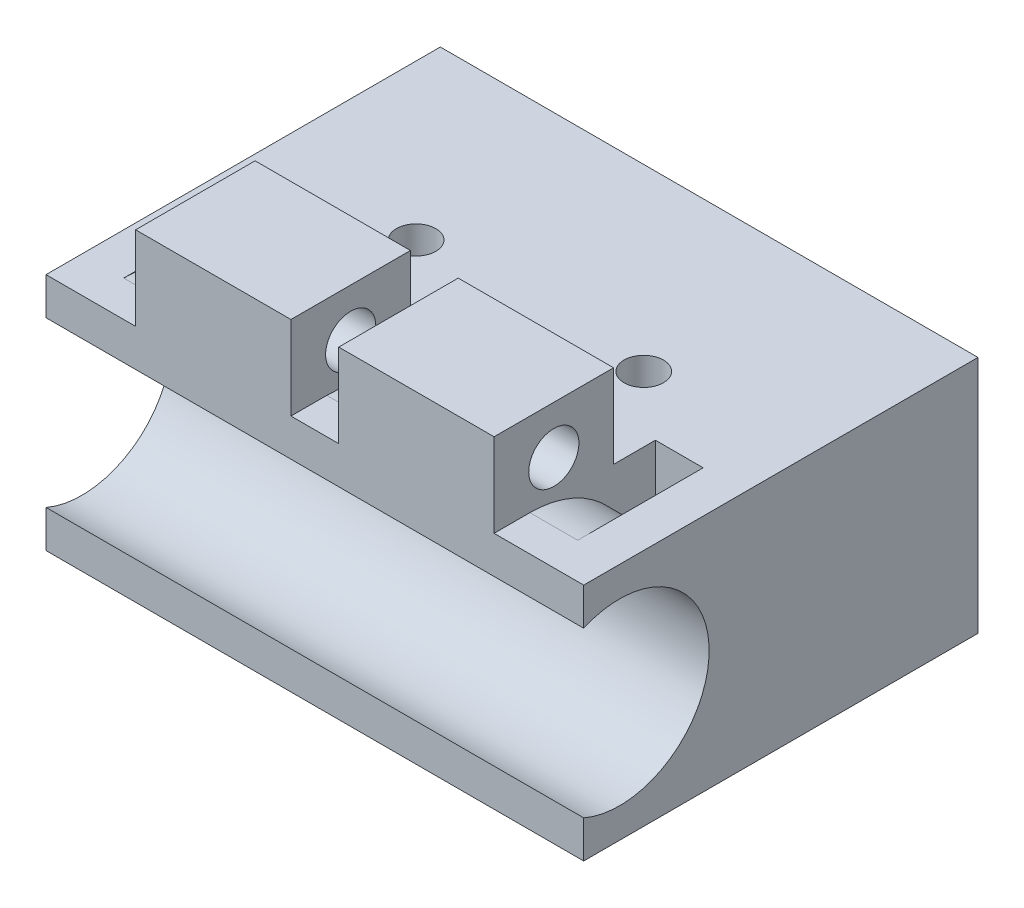
SolidWorks part; units mm, degrees
ref_plane "Front Plane" through (0, 0, 0) normal (0, 0, 1) x (1, 0, 0)
ref_plane "Top Plane" through (0, 0, 0) normal (0, 1, 0) x (1, 0, 0)
ref_plane "Right Plane" through (0, 0, 0) normal (1, 0, 0) x (0, 0, -1)
sketch "Sketch2" plane through (0, 0, 0) normal (0, 0, 1) x (1, 0, 0)
  line L1 (22.5, 10) -> (-22.5, 10)
  line L2 (22.5, 10) -> (22.5, -10)
  line L3 (22.5, -10) -> (-22.5, -10)
  line L4 (-22.5, 10) -> (-22.5, -10)
  line L5 (22.5, 10) -> (-22.5, -10) construction
  line L6 (22.5, -10) -> (-22.5, 10) construction
  point P0 (0, 0)
  dimension "D1" = 20
  dimension "D2" = 45
extrude "Boss-Extrude1" add sketch "Sketch2" along normal blind 33
sketch "Sketch3" plane through (22.5, 0, 0) normal (1, 0, 0) x (0, 0, -1)
  line L0 (-30, 0) -> (0, 0) construction
  circle A0 centre (-30, 0) radius 7.5
  dimension "D1" = 15
  dimension "D2" = 30
extrude "Cut-Extrude1" cut sketch "Sketch3" against normal blind 45
sketch "Sketch4" plane through (0, 0, 0) normal (0, 0, -1) x (-1, 0, 0)
  line L4 (22.5, -10) -> (22.5, 10)
  line L5 (22.5, 10) -> (-22.5, 10)
  line L6 (-22.5, 10) -> (-22.5, -10)
  line L7 (-22.5, -10) -> (22.5, -10)
  line L8 (22.5, -10) -> (22.5, 10)
  line L9 (22.5, 10) -> (-22.5, 10)
  line L10 (-22.5, 10) -> (-22.5, -10)
  line L11 (-22.5, -10) -> (22.5, -10)
  circle A0 centre (-15, 0) radius 4
  circle A1 centre (15, 0) radius 4
  dimension "D2" = 8
  dimension "D3" = 30
  dimension "D4" = 15
  dimension "D1" = 0
extrude "Cut-Extrude2" cut sketch "Sketch4" against normal blind 10 contours A0 | A1 region at (15, 0, 0) region at (-15, 0, 0)
sketch "Sketch5" plane through (0, -10, 0) normal (0, -1, 0) x (1, 0, 0)
  line L0 (0, 19.5) -> (0, 0) construction
  line L1 (-19, 21) -> (-15, 21)
  line L2 (-19, 21) -> (-19, 19.5)
  line L3 (-19, 19.5) -> (-15, 19.5)
  line L4 (-15, 21) -> (-15, 19.5)
  line L5 (-2, 19.5) -> (2, 19.5)
  line L6 (-2, 19.5) -> (-2, 21)
  line L7 (-2, 21) -> (2, 21)
  line L8 (2, 19.5) -> (2, 21)
  line L9 (15, 19.5) -> (19, 19.5)
  line L10 (15, 19.5) -> (15, 21)
  line L11 (15, 21) -> (19, 21)
  line L12 (19, 19.5) -> (19, 21)
  line L13 (-22.5, 19.5) -> (-19, 19.5) construction
  line L14 (-22.5, 33) -> (-22.5, 0) construction
  line L15 (-2, 19.5) -> (-15, 19.5) construction
  line L16 (2, 19.5) -> (15, 19.5) construction
  line L17 (19, 19.5) -> (22.5, 19.5) construction
  line L18 (22.5, 33) -> (22.5, 0) construction
  line L27 (-22.5, 0) -> (22.5, 0) construction
  dimension "D1" = 4
  dimension "D2" = 1.5
  dimension "D3" = 30
  dimension "D4" = 21
extrude "Cut-Extrude3" cut sketch "Sketch5" against normal blind 39
fillet "Fillet1" radius 9 3 edges at (17, -10, 21) (0, -10, 21) (-17, -10, 21)
hole_wizard "M4x0.7 Tapped Hole1" positions "Sketch7" profile "Sketch6" tap size "M4x0.7" standard "ANSI Metric" end condition through all
sketch "Sketch7" plane through (0, -10, 0) normal (0, -1, 0) x (-1, 0, 0)
  line L0 (0, 0) -> (0, -15) construction
  line L3 (9.525, -15) -> (-9.525, -15) construction
  point P0 (-9.525, -15)
  point P2 (9.525, -15)
  dimension "D1" = 19.05
  dimension "D2" = 15
cosmetic thread "Hole Thread1" parameters "D2"=4
cosmetic thread "Hole Thread2" parameters "D2"=4
sketch "Sketch6" plane through (9.525, -10, 15) normal (1, 0, 0) x (0, 0, -1)
  line L0 (0, 0) -> (0, 20)
  line L1 (0, 20) -> (1.65, 20)
  line L2 (1.65, 20) -> (1.65, 0)
  line L5 (1.65, 0) -> (0, 0)
  line L11 (0, -6.35) -> (0, 107.95) construction
  dimension "Thru Tap Drill Dia." = 3.3
  dimension "Thru Tap Drill Depth" = 20
sketch "Sketch8" plane through (0, -10, 0) normal (0, -1, 0) x (1, 0, 0)
  line L0 (-22.5, 33) -> (22.5, 33) construction
  line L1 (-15, 23) -> (-2, 23)
  line L2 (-15, 23) -> (-15, 33)
  line L3 (-15, 33) -> (-2, 33)
  line L4 (-2, 23) -> (-2, 33)
  line L5 (2, 23) -> (15, 23)
  line L6 (2, 23) -> (2, 33)
  line L7 (2, 33) -> (15, 33)
  line L8 (15, 23) -> (15, 33)
  line L9 (-15, 30) -> (-15, 21) construction
  line L13 (15, 21) -> (15, 30) construction
  line L14 (-2, 21) -> (-2, 30) construction
  dimension "D2" = 10
extrude "Boss-Extrude2" add sketch "Sketch8" along normal blind 7
sketch "Sketch14" plane through (-15, 0, 0) normal (-1, 0, 0) x (0, 0, 1)
  line L0 (33, -10) -> (0, -10) construction
  line L1 (28, -13) -> (28, -17) construction
  line L2 (33, -17) -> (23, -17) construction
  circle A0 centre (28, -13) radius 2.1
  dimension "D1" = 4.2
  dimension "D2" = 3
extrude "Cut-Extrude6" cut sketch "Sketch14" against normal through all
move or copy body "Body-Move/Copy1" bodies to move or copy 109 copy no rotation origin (0, -3.5, 0) rotation axis (0, 0, 1) rotation angle 180
hole_wizard "M3x0.5 Tapped Hole1" positions "Sketch15" profile "Sketch16" tap size "M3x0.5" standard "ANSI Metric"
sketch "Sketch15" plane through (0, -17, 0) normal (0, -1, 0) x (-1, 0, 0)
  line L0 (0, 0) -> (0, -5) construction
  line L3 (-9.525, -5) -> (9.525, -5) construction
  point P0 (9.525, -5)
  point P2 (-9.525, -5)
  dimension "D1" = 19.05
  dimension "D2" = 5
sketch "Sketch16" plane through (-9.525, -17, 5) normal (1, 0, 0) x (0, 0, -1)
  line L0 (0, 0) -> (0, 8.2511)
  line L1 (0, 8.2511) -> (1.25, 7.5)
  line L2 (1.25, 7.5) -> (1.25, 0)
  line L5 (1.25, 0) -> (0, 0)
  line L10 (0, 8.2511) -> (-1.25, 7.5) construction
  line L11 (0, -6.35) -> (0, 107.95) construction
  dimension "Tap Drill Dia." = 2.5
  dimension "Tap Drill Depth" = 7.5
  dimension "Drill Angle" = 118
cosmetic thread "Hole Thread3" parameters "D1"=6, "D2"=3
cosmetic thread "Hole Thread4" parameters "D1"=6, "D2"=3
